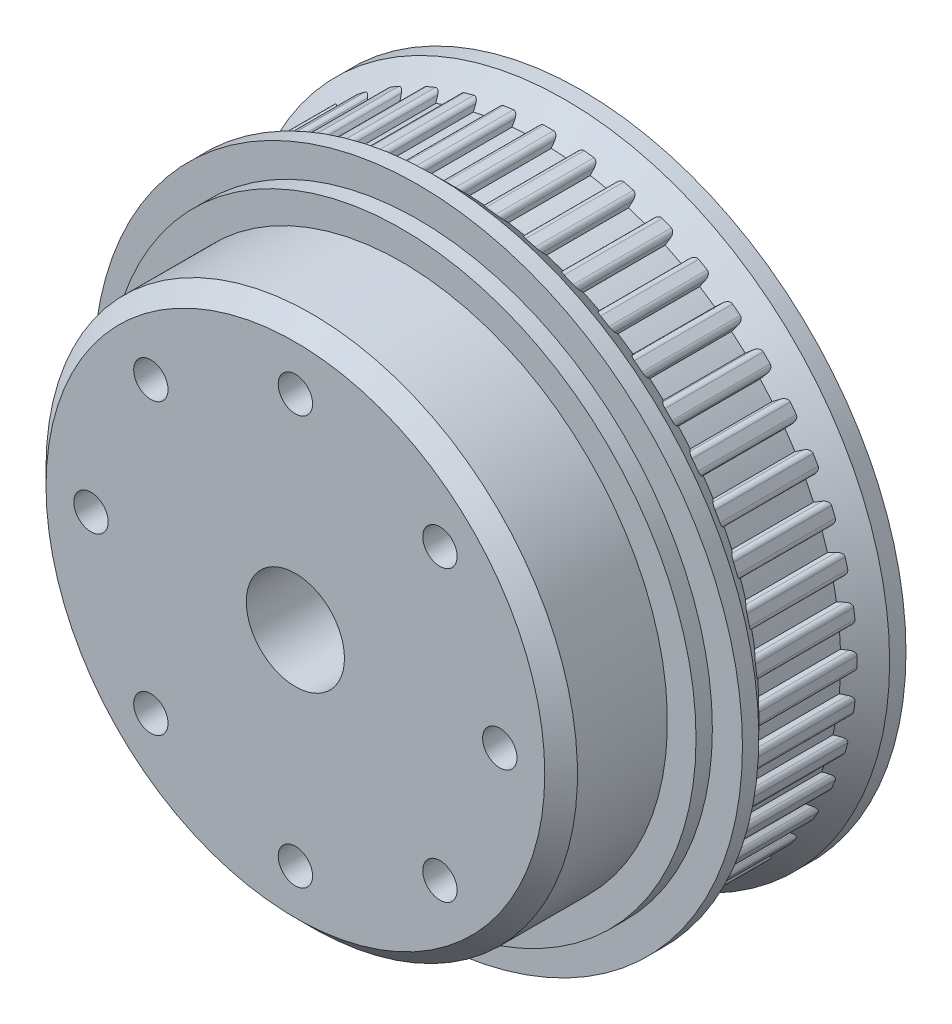
SolidWorks part; units mm, degrees
material "ABS"
ref_plane "Plan de face" through (0, 0, 0) normal (0, 0, 1) x (1, 0, 0)
ref_plane "Plan de dessus" through (0, 0, 0) normal (0, 1, 0) x (1, 0, 0)
ref_plane "Plan de droite" through (0, 0, 0) normal (1, 0, 0) x (0, 0, -1)
sketch "Esquisse1" plane through (0, 0, 0) normal (0, 0, 1) x (1, 0, 0)
  line L0 (0, 0) -> (0, 38.195) construction
  line L1 (0, 0) -> (4.9854, 37.8682) construction
  line L2 (1.3359, 36.4356) -> (3.4314, 36.2983)
  line L3 (0, 0) -> (2.3836, 36.367) construction
  line L4 (0, 37.6793) -> (0.5961, 37.6793)
  line L5 (1.1846, 37.1963) -> (1.3359, 36.4356)
  line L6 (4.9181, 37.3569) -> (4.3271, 37.4347)
  line L7 (3.6807, 37.0327) -> (3.4314, 36.2983)
  line L8 (6.0802, 35.9496) -> (8.1399, 35.5399)
  line L9 (4.9181, 37.3569) -> (5.5091, 37.2791)
  line L10 (6.0295, 36.7235) -> (6.0802, 35.9496)
  line L11 (9.7521, 36.3954) -> (9.1763, 36.5497)
  line L12 (8.4829, 36.2355) -> (8.1399, 35.5399)
  line L13 (10.7206, 34.8484) -> (12.7091, 34.1734)
  line L14 (9.7521, 36.3954) -> (10.3279, 36.2411)
  line L15 (10.7713, 35.6223) -> (10.7206, 34.8484)
  line L16 (14.4192, 34.8111) -> (13.8685, 35.0392)
  line L17 (13.14, 34.8182) -> (12.7091, 34.1734)
  line L18 (15.1775, 33.1509) -> (17.0609, 32.2221)
  line L19 (14.4192, 34.8111) -> (14.9699, 34.583)
  line L20 (15.3288, 33.9116) -> (15.1775, 33.1509)
  line L21 (18.8396, 32.6312) -> (18.3234, 32.9293)
  line L22 (17.5723, 32.8052) -> (17.0609, 32.2221)
  line L23 (19.3747, 30.8863) -> (21.1208, 29.7196)
  line L24 (18.8396, 32.6312) -> (19.3559, 32.3332)
  line L25 (19.624, 31.6207) -> (19.3747, 30.8863)
  line L26 (22.9377, 29.893) -> (22.4648, 30.2559)
  line L27 (21.7039, 30.2309) -> (21.1208, 29.7196)
  line L28 (23.2404, 28.0931) -> (24.8193, 26.7085)
  line L29 (22.9377, 29.893) -> (23.4106, 29.5301)
  line L30 (23.5835, 28.7887) -> (23.2404, 28.0931)
  line L31 (26.6433, 26.6433) -> (26.2218, 27.0648)
  line L32 (25.4642, 27.1394) -> (24.8193, 26.7085)
  line L33 (26.7085, 24.8193) -> (28.0931, 23.2404)
  line L34 (26.6433, 26.6433) -> (27.0648, 26.2218)
  line L35 (27.1394, 25.4642) -> (26.7085, 24.8193)
  line L36 (29.893, 22.9377) -> (29.5301, 23.4106)
  line L37 (28.7887, 23.5835) -> (28.0931, 23.2404)
  line L38 (29.7196, 21.1208) -> (30.8863, 19.3747)
  line L39 (29.893, 22.9377) -> (30.2559, 22.4648)
  line L40 (30.2309, 21.7039) -> (29.7196, 21.1208)
  line L41 (32.6312, 18.8396) -> (32.3332, 19.3559)
  line L42 (31.6207, 19.624) -> (30.8863, 19.3747)
  line L43 (32.2221, 17.0609) -> (33.1509, 15.1775)
  line L44 (32.6312, 18.8396) -> (32.9293, 18.3234)
  line L45 (32.8052, 17.5723) -> (32.2221, 17.0609)
  line L46 (34.8111, 14.4192) -> (34.583, 14.9699)
  line L47 (33.9116, 15.3288) -> (33.1509, 15.1775)
  line L48 (34.1734, 12.7091) -> (34.8484, 10.7206)
  line L49 (34.8111, 14.4192) -> (35.0392, 13.8685)
  line L50 (34.8182, 13.14) -> (34.1734, 12.7091)
  line L51 (36.3954, 9.7521) -> (36.2411, 10.3279)
  line L52 (35.6223, 10.7713) -> (34.8484, 10.7206)
  line L53 (35.5399, 8.1399) -> (35.9496, 6.0802)
  line L54 (36.3954, 9.7521) -> (36.5497, 9.1763)
  line L55 (36.2355, 8.4829) -> (35.5399, 8.1399)
  line L56 (37.3569, 4.9181) -> (37.2791, 5.5091)
  line L57 (36.7235, 6.0295) -> (35.9496, 6.0802)
  line L58 (36.2983, 3.4314) -> (36.4356, 1.3359)
  line L59 (37.3569, 4.9181) -> (37.4347, 4.3271)
  line L60 (37.0327, 3.6807) -> (36.2983, 3.4314)
  line L61 (37.6793, 0) -> (37.6793, 0.5961)
  line L62 (37.1963, 1.1846) -> (36.4356, 1.3359)
  line L63 (36.4356, -1.3359) -> (36.2983, -3.4314)
  line L64 (37.6793, 0) -> (37.6793, -0.5961)
  line L65 (37.1963, -1.1846) -> (36.4356, -1.3359)
  line L66 (37.3569, -4.9181) -> (37.4347, -4.3271)
  line L67 (37.0327, -3.6807) -> (36.2983, -3.4314)
  line L68 (35.9496, -6.0802) -> (35.5399, -8.1399)
  line L69 (37.3569, -4.9181) -> (37.2791, -5.5091)
  line L70 (36.7235, -6.0295) -> (35.9496, -6.0802)
  line L71 (36.3954, -9.7521) -> (36.5497, -9.1763)
  line L72 (36.2355, -8.4829) -> (35.5399, -8.1399)
  line L73 (34.8484, -10.7206) -> (34.1734, -12.7091)
  line L74 (36.3954, -9.7521) -> (36.2411, -10.3279)
  line L75 (35.6223, -10.7713) -> (34.8484, -10.7206)
  line L76 (34.8111, -14.4192) -> (35.0392, -13.8685)
  line L77 (34.8182, -13.14) -> (34.1734, -12.7091)
  line L78 (33.1509, -15.1775) -> (32.2221, -17.0609)
  line L79 (34.8111, -14.4192) -> (34.583, -14.9699)
  line L80 (33.9116, -15.3288) -> (33.1509, -15.1775)
  line L81 (32.6312, -18.8396) -> (32.9293, -18.3234)
  line L82 (32.8052, -17.5723) -> (32.2221, -17.0609)
  line L83 (30.8863, -19.3747) -> (29.7196, -21.1208)
  line L84 (32.6312, -18.8396) -> (32.3332, -19.3559)
  line L85 (31.6207, -19.624) -> (30.8863, -19.3747)
  line L86 (29.893, -22.9377) -> (30.2559, -22.4648)
  line L87 (30.2309, -21.7039) -> (29.7196, -21.1208)
  line L88 (28.0931, -23.2404) -> (26.7085, -24.8193)
  line L89 (29.893, -22.9377) -> (29.5301, -23.4106)
  line L90 (28.7887, -23.5835) -> (28.0931, -23.2404)
  line L91 (26.6433, -26.6433) -> (27.0648, -26.2218)
  line L92 (27.1394, -25.4642) -> (26.7085, -24.8193)
  line L93 (24.8193, -26.7085) -> (23.2404, -28.0931)
  line L94 (26.6433, -26.6433) -> (26.2218, -27.0648)
  line L95 (25.4642, -27.1394) -> (24.8193, -26.7085)
  line L96 (22.9377, -29.893) -> (23.4106, -29.5301)
  line L97 (23.5835, -28.7887) -> (23.2404, -28.0931)
  line L98 (21.1208, -29.7196) -> (19.3747, -30.8863)
  line L99 (22.9377, -29.893) -> (22.4648, -30.2559)
  line L100 (21.7039, -30.2309) -> (21.1208, -29.7196)
  line L101 (18.8396, -32.6312) -> (19.3559, -32.3332)
  line L102 (19.624, -31.6207) -> (19.3747, -30.8863)
  line L103 (17.0609, -32.2221) -> (15.1775, -33.1509)
  line L104 (18.8396, -32.6312) -> (18.3234, -32.9293)
  line L105 (17.5723, -32.8052) -> (17.0609, -32.2221)
  line L106 (14.4192, -34.8111) -> (14.9699, -34.583)
  line L107 (15.3288, -33.9116) -> (15.1775, -33.1509)
  line L108 (12.7091, -34.1734) -> (10.7206, -34.8484)
  line L109 (14.4192, -34.8111) -> (13.8685, -35.0392)
  line L110 (13.14, -34.8182) -> (12.7091, -34.1734)
  line L111 (9.7521, -36.3954) -> (10.3279, -36.2411)
  line L112 (10.7713, -35.6223) -> (10.7206, -34.8484)
  line L113 (8.1399, -35.5399) -> (6.0802, -35.9496)
  line L114 (9.7521, -36.3954) -> (9.1763, -36.5497)
  line L115 (8.4829, -36.2355) -> (8.1399, -35.5399)
  line L116 (4.9181, -37.3569) -> (5.5091, -37.2791)
  line L117 (6.0295, -36.7235) -> (6.0802, -35.9496)
  line L118 (3.4314, -36.2983) -> (1.3359, -36.4356)
  line L119 (4.9181, -37.3569) -> (4.3271, -37.4347)
  line L120 (3.6807, -37.0327) -> (3.4314, -36.2983)
  line L121 (0, -37.6793) -> (0.5961, -37.6793)
  line L122 (1.1846, -37.1963) -> (1.3359, -36.4356)
  line L123 (-1.3359, -36.4356) -> (-3.4314, -36.2983)
  line L124 (0, -37.6793) -> (-0.5961, -37.6793)
  line L125 (-1.1846, -37.1963) -> (-1.3359, -36.4356)
  line L126 (-4.9181, -37.3569) -> (-4.3271, -37.4347)
  line L127 (-3.6807, -37.0327) -> (-3.4314, -36.2983)
  line L128 (-6.0802, -35.9496) -> (-8.1399, -35.5399)
  line L129 (-4.9181, -37.3569) -> (-5.5091, -37.2791)
  line L130 (-6.0295, -36.7235) -> (-6.0802, -35.9496)
  line L131 (-9.7521, -36.3954) -> (-9.1763, -36.5497)
  line L132 (-8.4829, -36.2355) -> (-8.1399, -35.5399)
  line L133 (-10.7206, -34.8484) -> (-12.7091, -34.1734)
  line L134 (-9.7521, -36.3954) -> (-10.3279, -36.2411)
  line L135 (-10.7713, -35.6223) -> (-10.7206, -34.8484)
  line L136 (-14.4192, -34.8111) -> (-13.8685, -35.0392)
  line L137 (-13.14, -34.8182) -> (-12.7091, -34.1734)
  line L138 (-15.1775, -33.1509) -> (-17.0609, -32.2221)
  line L139 (-14.4192, -34.8111) -> (-14.9699, -34.583)
  line L140 (-15.3288, -33.9116) -> (-15.1775, -33.1509)
  line L141 (-18.8396, -32.6312) -> (-18.3234, -32.9293)
  line L142 (-17.5723, -32.8052) -> (-17.0609, -32.2221)
  line L143 (-19.3747, -30.8863) -> (-21.1208, -29.7196)
  line L144 (-18.8396, -32.6312) -> (-19.3559, -32.3332)
  line L145 (-19.624, -31.6207) -> (-19.3747, -30.8863)
  line L146 (-22.9377, -29.893) -> (-22.4648, -30.2559)
  line L147 (-21.7039, -30.2309) -> (-21.1208, -29.7196)
  line L148 (-23.2404, -28.0931) -> (-24.8193, -26.7085)
  line L149 (-22.9377, -29.893) -> (-23.4106, -29.5301)
  line L150 (-23.5835, -28.7887) -> (-23.2404, -28.0931)
  line L151 (-26.6433, -26.6433) -> (-26.2218, -27.0648)
  line L152 (-25.4642, -27.1394) -> (-24.8193, -26.7085)
  line L153 (-26.7085, -24.8193) -> (-28.0931, -23.2404)
  line L154 (-26.6433, -26.6433) -> (-27.0648, -26.2218)
  line L155 (-27.1394, -25.4642) -> (-26.7085, -24.8193)
  line L156 (-29.893, -22.9377) -> (-29.5301, -23.4106)
  line L157 (-28.7887, -23.5835) -> (-28.0931, -23.2404)
  line L158 (-29.7196, -21.1208) -> (-30.8863, -19.3747)
  line L159 (-29.893, -22.9377) -> (-30.2559, -22.4648)
  line L160 (-30.2309, -21.7039) -> (-29.7196, -21.1208)
  line L161 (-32.6312, -18.8396) -> (-32.3332, -19.3559)
  line L162 (-31.6207, -19.624) -> (-30.8863, -19.3747)
  line L163 (-32.2221, -17.0609) -> (-33.1509, -15.1775)
  line L164 (-32.6312, -18.8396) -> (-32.9293, -18.3234)
  line L165 (-32.8052, -17.5723) -> (-32.2221, -17.0609)
  line L166 (-34.8111, -14.4192) -> (-34.583, -14.9699)
  line L167 (-33.9116, -15.3288) -> (-33.1509, -15.1775)
  line L168 (-34.1734, -12.7091) -> (-34.8484, -10.7206)
  line L169 (-34.8111, -14.4192) -> (-35.0392, -13.8685)
  line L170 (-34.8182, -13.14) -> (-34.1734, -12.7091)
  line L171 (-36.3954, -9.7521) -> (-36.2411, -10.3279)
  line L172 (-35.6223, -10.7713) -> (-34.8484, -10.7206)
  line L173 (-35.5399, -8.1399) -> (-35.9496, -6.0802)
  line L174 (-36.3954, -9.7521) -> (-36.5497, -9.1763)
  line L175 (-36.2355, -8.4829) -> (-35.5399, -8.1399)
  line L176 (-37.3569, -4.9181) -> (-37.2791, -5.5091)
  line L177 (-36.7235, -6.0295) -> (-35.9496, -6.0802)
  line L178 (-36.2983, -3.4314) -> (-36.4356, -1.3359)
  line L179 (-37.3569, -4.9181) -> (-37.4347, -4.3271)
  line L180 (-37.0327, -3.6807) -> (-36.2983, -3.4314)
  line L181 (-37.6793, 0) -> (-37.6793, -0.5961)
  line L182 (-37.1963, -1.1846) -> (-36.4356, -1.3359)
  line L183 (-36.4356, 1.3359) -> (-36.2983, 3.4314)
  line L184 (-37.6793, 0) -> (-37.6793, 0.5961)
  line L185 (-37.1963, 1.1846) -> (-36.4356, 1.3359)
  line L186 (-37.3569, 4.9181) -> (-37.4347, 4.3271)
  line L187 (-37.0327, 3.6807) -> (-36.2983, 3.4314)
  line L188 (-35.9496, 6.0802) -> (-35.5399, 8.1399)
  line L189 (-37.3569, 4.9181) -> (-37.2791, 5.5091)
  line L190 (-36.7235, 6.0295) -> (-35.9496, 6.0802)
  line L191 (-36.3954, 9.7521) -> (-36.5497, 9.1763)
  line L192 (-36.2355, 8.4829) -> (-35.5399, 8.1399)
  line L193 (-34.8484, 10.7206) -> (-34.1734, 12.7091)
  line L194 (-36.3954, 9.7521) -> (-36.2411, 10.3279)
  line L195 (-35.6223, 10.7713) -> (-34.8484, 10.7206)
  line L196 (-34.8111, 14.4192) -> (-35.0392, 13.8685)
  line L197 (-34.8182, 13.14) -> (-34.1734, 12.7091)
  line L198 (-33.1509, 15.1775) -> (-32.2221, 17.0609)
  line L199 (-34.8111, 14.4192) -> (-34.583, 14.9699)
  line L200 (-33.9116, 15.3288) -> (-33.1509, 15.1775)
  line L201 (-32.6312, 18.8396) -> (-32.9293, 18.3234)
  line L202 (-32.8052, 17.5723) -> (-32.2221, 17.0609)
  line L203 (-30.8863, 19.3747) -> (-29.7196, 21.1208)
  line L204 (-32.6312, 18.8396) -> (-32.3332, 19.3559)
  line L205 (-31.6207, 19.624) -> (-30.8863, 19.3747)
  line L206 (-29.893, 22.9377) -> (-30.2559, 22.4648)
  line L207 (-30.2309, 21.7039) -> (-29.7196, 21.1208)
  line L208 (-28.0931, 23.2404) -> (-26.7085, 24.8193)
  line L209 (-29.893, 22.9377) -> (-29.5301, 23.4106)
  line L210 (-28.7887, 23.5835) -> (-28.0931, 23.2404)
  line L211 (-26.6433, 26.6433) -> (-27.0648, 26.2218)
  line L212 (-27.1394, 25.4642) -> (-26.7085, 24.8193)
  line L213 (-24.8193, 26.7085) -> (-23.2404, 28.0931)
  line L214 (-26.6433, 26.6433) -> (-26.2218, 27.0648)
  line L215 (-25.4642, 27.1394) -> (-24.8193, 26.7085)
  line L216 (-22.9377, 29.893) -> (-23.4106, 29.5301)
  line L217 (-23.5835, 28.7887) -> (-23.2404, 28.0931)
  line L218 (-21.1208, 29.7196) -> (-19.3747, 30.8863)
  line L219 (-22.9377, 29.893) -> (-22.4648, 30.2559)
  line L220 (-21.7039, 30.2309) -> (-21.1208, 29.7196)
  line L221 (-18.8396, 32.6312) -> (-19.3559, 32.3332)
  line L222 (-19.624, 31.6207) -> (-19.3747, 30.8863)
  line L223 (-17.0609, 32.2221) -> (-15.1775, 33.1509)
  line L224 (-18.8396, 32.6312) -> (-18.3234, 32.9293)
  line L225 (-17.5723, 32.8052) -> (-17.0609, 32.2221)
  line L226 (-14.4192, 34.8111) -> (-14.9699, 34.583)
  line L227 (-15.3288, 33.9116) -> (-15.1775, 33.1509)
  line L228 (-12.7091, 34.1734) -> (-10.7206, 34.8484)
  line L229 (-14.4192, 34.8111) -> (-13.8685, 35.0392)
  line L230 (-13.14, 34.8182) -> (-12.7091, 34.1734)
  line L231 (-9.7521, 36.3954) -> (-10.3279, 36.2411)
  line L232 (-10.7713, 35.6223) -> (-10.7206, 34.8484)
  line L233 (-8.1399, 35.5399) -> (-6.0802, 35.9496)
  line L234 (-9.7521, 36.3954) -> (-9.1763, 36.5497)
  line L235 (-8.4829, 36.2355) -> (-8.1399, 35.5399)
  line L236 (-4.9181, 37.3569) -> (-5.5091, 37.2791)
  line L237 (-6.0295, 36.7235) -> (-6.0802, 35.9496)
  line L238 (-3.4314, 36.2983) -> (-1.3359, 36.4356)
  line L239 (-4.9181, 37.3569) -> (-4.3271, 37.4347)
  line L240 (-3.6807, 37.0327) -> (-3.4314, 36.2983)
  line L241 (0, 37.6793) -> (-0.5961, 37.6793)
  line L242 (-1.1846, 37.1963) -> (-1.3359, 36.4356)
  circle A0 centre (0, 0) radius 38.195 construction
  circle A1 centre (0, 0) radius 37.695 construction
  circle A2 centre (0, 0) radius 36.445 construction
  arc A3 (4.3271, 37.4347) -> (3.6807, 37.0327) centre (4.2488, 36.8399) ccw
  arc A4 (1.1846, 37.1963) -> (0.5961, 37.6793) centre (0.5961, 37.0793) ccw
  arc A5 (9.1763, 36.5497) -> (8.4829, 36.2355) centre (9.0211, 35.9701) ccw
  arc A6 (6.0295, 36.7235) -> (5.5091, 37.2791) centre (5.4308, 36.6843) ccw
  arc A7 (13.8685, 35.0392) -> (13.14, 34.8182) centre (13.6389, 34.4849) ccw
  arc A8 (10.7713, 35.6223) -> (10.3279, 36.2411) centre (10.1726, 35.6616) ccw
  arc A9 (18.3234, 32.9293) -> (17.5723, 32.8052) centre (18.0234, 32.4096) ccw
  arc A10 (15.3288, 33.9116) -> (14.9699, 34.583) centre (14.7403, 34.0287) ccw
  arc A11 (22.4648, 30.2559) -> (21.7039, 30.2309) centre (22.0995, 29.7798) ccw
  arc A12 (19.624, 31.6207) -> (19.3559, 32.3332) centre (19.0559, 31.8136) ccw
  arc A13 (26.2218, 27.0648) -> (25.4642, 27.1394) centre (25.7975, 26.6405) ccw
  arc A14 (23.5835, 28.7887) -> (23.4106, 29.5301) centre (23.0453, 29.0541) ccw
  arc A15 (29.5301, 23.4106) -> (28.7887, 23.5835) centre (29.0541, 23.0453) ccw
  arc A16 (27.1394, 25.4642) -> (27.0648, 26.2218) centre (26.6405, 25.7975) ccw
  arc A17 (32.3332, 19.3559) -> (31.6207, 19.624) centre (31.8136, 19.0559) ccw
  arc A18 (30.2309, 21.7039) -> (30.2559, 22.4648) centre (29.7798, 22.0995) ccw
  arc A19 (34.583, 14.9699) -> (33.9116, 15.3288) centre (34.0287, 14.7403) ccw
  arc A20 (32.8052, 17.5723) -> (32.9293, 18.3234) centre (32.4096, 18.0234) ccw
  arc A21 (36.2411, 10.3279) -> (35.6223, 10.7713) centre (35.6616, 10.1726) ccw
  arc A22 (34.8182, 13.14) -> (35.0392, 13.8685) centre (34.4849, 13.6389) ccw
  arc A23 (37.2791, 5.5091) -> (36.7235, 6.0295) centre (36.6843, 5.4308) ccw
  arc A24 (36.2355, 8.4829) -> (36.5497, 9.1763) centre (35.9701, 9.0211) ccw
  arc A25 (37.6793, 0.5961) -> (37.1963, 1.1846) centre (37.0793, 0.5961) ccw
  arc A26 (37.0327, 3.6807) -> (37.4347, 4.3271) centre (36.8399, 4.2488) ccw
  arc A27 (37.4347, -4.3271) -> (37.0327, -3.6807) centre (36.8399, -4.2488) ccw
  arc A28 (37.1963, -1.1846) -> (37.6793, -0.5961) centre (37.0793, -0.5961) ccw
  arc A29 (36.5497, -9.1763) -> (36.2355, -8.4829) centre (35.9701, -9.0211) ccw
  arc A30 (36.7235, -6.0295) -> (37.2791, -5.5091) centre (36.6843, -5.4308) ccw
  arc A31 (35.0392, -13.8685) -> (34.8182, -13.14) centre (34.4849, -13.6389) ccw
  arc A32 (35.6223, -10.7713) -> (36.2411, -10.3279) centre (35.6616, -10.1726) ccw
  arc A33 (32.9293, -18.3234) -> (32.8052, -17.5723) centre (32.4096, -18.0234) ccw
  arc A34 (33.9116, -15.3288) -> (34.583, -14.9699) centre (34.0287, -14.7403) ccw
  arc A35 (30.2559, -22.4648) -> (30.2309, -21.7039) centre (29.7798, -22.0995) ccw
  arc A36 (31.6207, -19.624) -> (32.3332, -19.3559) centre (31.8136, -19.0559) ccw
  arc A37 (27.0648, -26.2218) -> (27.1394, -25.4642) centre (26.6405, -25.7975) ccw
  arc A38 (28.7887, -23.5835) -> (29.5301, -23.4106) centre (29.0541, -23.0453) ccw
  arc A39 (23.4106, -29.5301) -> (23.5835, -28.7887) centre (23.0453, -29.0541) ccw
  arc A40 (25.4642, -27.1394) -> (26.2218, -27.0648) centre (25.7975, -26.6405) ccw
  arc A41 (19.3559, -32.3332) -> (19.624, -31.6207) centre (19.0559, -31.8136) ccw
  arc A42 (21.7039, -30.2309) -> (22.4648, -30.2559) centre (22.0995, -29.7798) ccw
  arc A43 (14.9699, -34.583) -> (15.3288, -33.9116) centre (14.7403, -34.0287) ccw
  arc A44 (17.5723, -32.8052) -> (18.3234, -32.9293) centre (18.0234, -32.4096) ccw
  arc A45 (10.3279, -36.2411) -> (10.7713, -35.6223) centre (10.1726, -35.6616) ccw
  arc A46 (13.14, -34.8182) -> (13.8685, -35.0392) centre (13.6389, -34.4849) ccw
  arc A47 (5.5091, -37.2791) -> (6.0295, -36.7235) centre (5.4308, -36.6843) ccw
  arc A48 (8.4829, -36.2355) -> (9.1763, -36.5497) centre (9.0211, -35.9701) ccw
  arc A49 (0.5961, -37.6793) -> (1.1846, -37.1963) centre (0.5961, -37.0793) ccw
  arc A50 (3.6807, -37.0327) -> (4.3271, -37.4347) centre (4.2488, -36.8399) ccw
  arc A51 (-4.3271, -37.4347) -> (-3.6807, -37.0327) centre (-4.2488, -36.8399) ccw
  arc A52 (-1.1846, -37.1963) -> (-0.5961, -37.6793) centre (-0.5961, -37.0793) ccw
  arc A53 (-9.1763, -36.5497) -> (-8.4829, -36.2355) centre (-9.0211, -35.9701) ccw
  arc A54 (-6.0295, -36.7235) -> (-5.5091, -37.2791) centre (-5.4308, -36.6843) ccw
  arc A55 (-13.8685, -35.0392) -> (-13.14, -34.8182) centre (-13.6389, -34.4849) ccw
  arc A56 (-10.7713, -35.6223) -> (-10.3279, -36.2411) centre (-10.1726, -35.6616) ccw
  arc A57 (-18.3234, -32.9293) -> (-17.5723, -32.8052) centre (-18.0234, -32.4096) ccw
  arc A58 (-15.3288, -33.9116) -> (-14.9699, -34.583) centre (-14.7403, -34.0287) ccw
  arc A59 (-22.4648, -30.2559) -> (-21.7039, -30.2309) centre (-22.0995, -29.7798) ccw
  arc A60 (-19.624, -31.6207) -> (-19.3559, -32.3332) centre (-19.0559, -31.8136) ccw
  arc A61 (-26.2218, -27.0648) -> (-25.4642, -27.1394) centre (-25.7975, -26.6405) ccw
  arc A62 (-23.5835, -28.7887) -> (-23.4106, -29.5301) centre (-23.0453, -29.0541) ccw
  arc A63 (-29.5301, -23.4106) -> (-28.7887, -23.5835) centre (-29.0541, -23.0453) ccw
  arc A64 (-27.1394, -25.4642) -> (-27.0648, -26.2218) centre (-26.6405, -25.7975) ccw
  arc A65 (-32.3332, -19.3559) -> (-31.6207, -19.624) centre (-31.8136, -19.0559) ccw
  arc A66 (-30.2309, -21.7039) -> (-30.2559, -22.4648) centre (-29.7798, -22.0995) ccw
  arc A67 (-34.583, -14.9699) -> (-33.9116, -15.3288) centre (-34.0287, -14.7403) ccw
  arc A68 (-32.8052, -17.5723) -> (-32.9293, -18.3234) centre (-32.4096, -18.0234) ccw
  arc A69 (-36.2411, -10.3279) -> (-35.6223, -10.7713) centre (-35.6616, -10.1726) ccw
  arc A70 (-34.8182, -13.14) -> (-35.0392, -13.8685) centre (-34.4849, -13.6389) ccw
  arc A71 (-37.2791, -5.5091) -> (-36.7235, -6.0295) centre (-36.6843, -5.4308) ccw
  arc A72 (-36.2355, -8.4829) -> (-36.5497, -9.1763) centre (-35.9701, -9.0211) ccw
  arc A73 (-37.6793, -0.5961) -> (-37.1963, -1.1846) centre (-37.0793, -0.5961) ccw
  arc A74 (-37.0327, -3.6807) -> (-37.4347, -4.3271) centre (-36.8399, -4.2488) ccw
  arc A75 (-37.4347, 4.3271) -> (-37.0327, 3.6807) centre (-36.8399, 4.2488) ccw
  arc A76 (-37.1963, 1.1846) -> (-37.6793, 0.5961) centre (-37.0793, 0.5961) ccw
  arc A77 (-36.5497, 9.1763) -> (-36.2355, 8.4829) centre (-35.9701, 9.0211) ccw
  arc A78 (-36.7235, 6.0295) -> (-37.2791, 5.5091) centre (-36.6843, 5.4308) ccw
  arc A79 (-35.0392, 13.8685) -> (-34.8182, 13.14) centre (-34.4849, 13.6389) ccw
  arc A80 (-35.6223, 10.7713) -> (-36.2411, 10.3279) centre (-35.6616, 10.1726) ccw
  arc A81 (-32.9293, 18.3234) -> (-32.8052, 17.5723) centre (-32.4096, 18.0234) ccw
  arc A82 (-33.9116, 15.3288) -> (-34.583, 14.9699) centre (-34.0287, 14.7403) ccw
  arc A83 (-30.2559, 22.4648) -> (-30.2309, 21.7039) centre (-29.7798, 22.0995) ccw
  arc A84 (-31.6207, 19.624) -> (-32.3332, 19.3559) centre (-31.8136, 19.0559) ccw
  arc A85 (-27.0648, 26.2218) -> (-27.1394, 25.4642) centre (-26.6405, 25.7975) ccw
  arc A86 (-28.7887, 23.5835) -> (-29.5301, 23.4106) centre (-29.0541, 23.0453) ccw
  arc A87 (-23.4106, 29.5301) -> (-23.5835, 28.7887) centre (-23.0453, 29.0541) ccw
  arc A88 (-25.4642, 27.1394) -> (-26.2218, 27.0648) centre (-25.7975, 26.6405) ccw
  arc A89 (-19.3559, 32.3332) -> (-19.624, 31.6207) centre (-19.0559, 31.8136) ccw
  arc A90 (-21.7039, 30.2309) -> (-22.4648, 30.2559) centre (-22.0995, 29.7798) ccw
  arc A91 (-14.9699, 34.583) -> (-15.3288, 33.9116) centre (-14.7403, 34.0287) ccw
  arc A92 (-17.5723, 32.8052) -> (-18.3234, 32.9293) centre (-18.0234, 32.4096) ccw
  arc A93 (-10.3279, 36.2411) -> (-10.7713, 35.6223) centre (-10.1726, 35.6616) ccw
  arc A94 (-13.14, 34.8182) -> (-13.8685, 35.0392) centre (-13.6389, 34.4849) ccw
  arc A95 (-5.5091, 37.2791) -> (-6.0295, 36.7235) centre (-5.4308, 36.6843) ccw
  arc A96 (-8.4829, 36.2355) -> (-9.1763, 36.5497) centre (-9.0211, 35.9701) ccw
  arc A97 (-0.5961, 37.6793) -> (-1.1846, 37.1963) centre (-0.5961, 37.0793) ccw
  arc A98 (-3.6807, 37.0327) -> (-4.3271, 37.4347) centre (-4.2488, 36.8399) ccw
  circle A99 centre (0, 0) radius 30
  point P22 (3.839, 37.499)
  point P25 (1.0885, 37.6793)
  point P492 (0, 0)
  dimension "D1" = 76.39
  dimension "D3" = 0.5
  dimension "D4" = 1.25
  dimension "D9" = 0.6
  dimension "D11" = 60
  dimension "D2" = 7.5
  dimension "D5" = 3.75
  dimension "D6" = 15
  dimension "D7" = 15
  dimension "D8" = 2.1
  dimension "D10" = 48
extrude "Boss.-Extru.1" add sketch "Esquisse1" along normal blind 16
sketch "Esquisse2" plane through (0, 0, 0) normal (0, 1, 0) x (1, 0, 0)
  line L0 (0, 0) -> (0, -16) construction
  line L2 (0.5961, -16) -> (-0.5961, -16) construction
  line L4 (-6, 2) -> (-6, -18)
  line L5 (-6, -18) -> (-39.6793, -18)
  line L6 (-39.6793, -18) -> (-39.6793, -16)
  line L7 (-39.6793, -16) -> (-36.6793, -13)
  line L8 (-36.6793, -13) -> (-36.6793, -3)
  line L9 (-36.6793, -3) -> (-39.6793, 0)
  line L10 (-39.6793, 0) -> (-39.6793, 2)
  line L11 (-39.6793, 2) -> (-6, 2)
  line L12 (0, -8) -> (-6, -8) construction
  line L13 (-37.6793, -16) -> (-37.6793, 0) construction
  dimension "D1" = 2
  dimension "D2" = 45
  dimension "D3" = 2
  dimension "D4" = 45
  dimension "D5" = 20
  dimension "D6" = 2
  dimension "D7" = 6
  dimension "D8" = 10
revolve "Révolution1" add sketch "Esquisse2" angle 360 about L0
sketch "Esquisse4" plane through (0, 0, 18) normal (0, 0, 1) x (1, 0, 0)
  circle A0 centre (0, 0) radius 36
  circle A2 centre (0, 0) radius 6
  dimension "D1" = 72
  dimension "D2" = 12
extrude "Boss.-Extru.2" add sketch "Esquisse4" along normal blind 2
sketch "Esquisse5" plane through (0, 0, 20) normal (0, 0, 1) x (1, 0, 0)
  circle A0 centre (0, 0) radius 6 construction
  circle A1 centre (0, 0) radius 6
  circle A2 centre (0, 0) radius 32.5
  dimension "D1" = 65
extrude "Boss.-Extru.3" add sketch "Esquisse5" along normal blind 13
sketch "Esquisse3" plane through (0, 0, -2) normal (0, 0, -1) x (-1, 0, 0)
  circle A0 centre (0, 0) radius 25 construction
  circle A1 centre (0, 25) radius 2.1
  circle A2 centre (17.6777, 17.6777) radius 2.1
  circle A3 centre (25, 0) radius 2.1
  circle A4 centre (17.6777, -17.6777) radius 2.1
  circle A5 centre (0, -25) radius 2.1
  circle A6 centre (-17.6777, -17.6777) radius 2.1
  circle A7 centre (-25, 0) radius 2.1
  circle A8 centre (-17.6777, 17.6777) radius 2.1
  point P21 (0, 0)
  dimension "D1" = 50
  dimension "D2" = 4.2
  dimension "D3" = 8
extrude "Enlèv. mat.-Extru.1" cut sketch "Esquisse3" against normal through all
sketch "Esquisse6" plane through (0, 0, 33) normal (0, 0, 1) x (1, 0, 0)
  line L0 (-25, 0) -> (0, 0) construction
  line L1 (0, 0) -> (-23.097, 9.5671) construction
  circle A0 centre (0, 0) radius 15 construction
  circle A1 centre (0, 15) radius 4
  circle A2 centre (10.6066, 10.6066) radius 4
  circle A3 centre (15, 0) radius 4
  circle A4 centre (10.6066, -10.6066) radius 4
  circle A5 centre (0, -15) radius 4
  circle A6 centre (-10.6066, -10.6066) radius 4
  circle A7 centre (-15, 0) radius 4
  circle A8 centre (-10.6066, 10.6066) radius 4
  circle A9 centre (0, 0) radius 25 construction
  circle A10 centre (-23.097, 9.5671) radius 4
  circle A11 centre (-9.5671, 23.097) radius 4
  circle A12 centre (9.5671, 23.097) radius 4
  circle A13 centre (23.097, 9.5671) radius 4
  circle A14 centre (23.097, -9.5671) radius 4
  circle A15 centre (9.5671, -23.097) radius 4
  circle A16 centre (-9.5671, -23.097) radius 4
  circle A17 centre (-23.097, -9.5671) radius 4
  point P20 (0, 0)
  point P24 (0, 0)
  point P25 (0, 0)
  point P40 (0, 0)
  dimension "D1" = 30
  dimension "D2" = 8
  dimension "D4" = 50
  dimension "D5" = 8
  dimension "D6" = 22.5
  dimension "D3" = 8
  dimension "D7" = 8
extrude "Enlèv. mat.-Extru.2" [suppressed] cut sketch "Esquisse6" against normal through all
chamfer "Chanfrein1" distance 2 angle 45 1 edges at (32.5, 0, 33)
